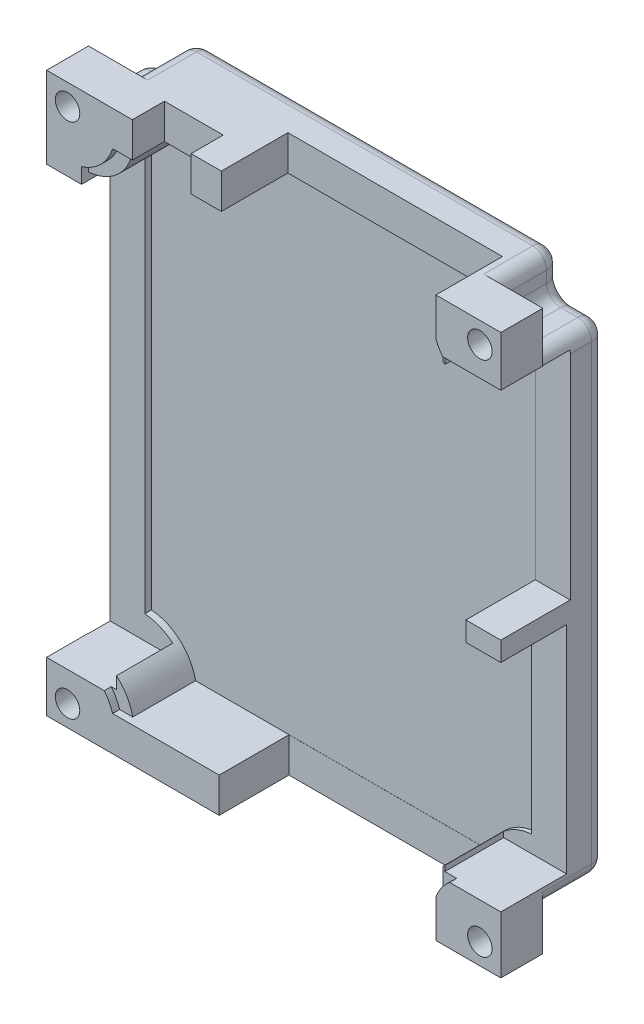
SolidWorks part; units mm, degrees
ref_plane "Front Plane" through (0, 0, 0) normal (0, 0, 1) x (1, 0, 0)
ref_plane "Top Plane" through (0, 0, 0) normal (0, 1, 0) x (1, 0, 0)
ref_plane "Right Plane" through (0, 0, 0) normal (1, 0, 0) x (0, 0, -1)
sketch "Sketch1" plane through (0, 0, 0) normal (0, 0, 1) x (1, 0, 0)
  line L0 (-65, 80) -> (-65, 0)
  line L9 (0, 0) -> (-65, 0)
  line L10 (0, 0) -> (0, 80)
  line L11 (0, 80) -> (-65, 80)
extrude "Boss-Extrude1" add sketch "Sketch1" against normal blind 15
sketch "Sketch2" plane through (0, 0, 0) normal (0, 0, 1) x (1, 0, 0)
  circle A0 centre (-3, 3) radius 1.75
  circle A1 centre (-62, 3) radius 1.75
  circle A2 centre (-62, 77) radius 1.75
  circle A3 centre (-3, 77) radius 1.75
  dimension "D1" = 3.5
  dimension "D2" = 3.5
  dimension "D3" = 3.5
extrude "Cut-Extrude1" cut sketch "Sketch2" against normal up to surface (15 mm away) up to face at (-32.5, 40, -15)
sketch "Sketch3" plane through (0, 0, -15) normal (0, 0, -1) x (-1, 0, 0)
  line L0 (0, 80) -> (65, 80) construction
  line L1 (0, 80) -> (6.4525, 80)
  line L2 (0, 80) -> (0, 74.3584)
  line L3 (0, 74.3584) -> (6.4525, 74.3584)
  line L4 (6.4525, 80) -> (6.4525, 74.3584)
  line L5 (58.5475, 80) -> (65, 80)
  line L6 (58.5475, 80) -> (58.5475, 74.3584)
  line L7 (58.5475, 74.3584) -> (65, 74.3584)
  line L8 (65, 80) -> (65, 74.3584)
  line L9 (65, 80) -> (65, 0) construction
  line L10 (0, 0) -> (0, 80) construction
  line L11 (0, 5.6416) -> (6.4525, 5.6416)
  line L12 (0, 5.6416) -> (0, 0)
  line L13 (0, 0) -> (6.4525, 0)
  line L14 (6.4525, 5.6416) -> (6.4525, 0)
  line L15 (65, 0) -> (0, 0) construction
  line L17 (58.5475, 0) -> (65, 0)
  line L18 (58.5475, 0) -> (58.5475, 5.6416)
  line L19 (58.5475, 5.6416) -> (65, 5.6416)
  line L20 (65, 0) -> (65, 5.6416)
  dimension "D1" = 6.4525
  dimension "D2" = 5.6416
  dimension "D3" = 5.6416
  dimension "D4" = 6.4525
  dimension "D5" = 6.4525
  dimension "D6" = 6.4525
  dimension "D7" = 5.6416
  dimension "D8" = 5.6416
extrude "Cut-Extrude2" cut sketch "Sketch3" against normal blind 9
fillet "Fillet1" radius 2 24 edges at (-3.2263, 74.3584, -15) (-6.4525, 77.1792, -15) (-58.5475, 77.1792, -15) (0, 5.6416, -10.5) (-6.4525, 0, -10.5) (-6.4525, 80, -10.5) (0, 74.3584, -10.5) (-58.5475, 0, -10.5) (-65, 5.6416, -10.5) (-58.5475, 80, -10.5) (-65, 74.3584, -10.5) (-58.5475, 74.3584, -10.5) (-61.7737, 74.3584, -15) (-32.5, 80, -15) (0, 40, -15) (-3.2263, 5.6416, -15) (-6.4525, 2.8208, -15) (-32.5, 0, -15) (-65, 40, -15) (-58.5475, 2.8208, -15) (-61.7737, 5.6416, -15) (-58.5475, 5.6416, -10.5) (-6.4525, 5.6416, -10.5) (-6.4525, 74.3584, -10.5)
shell "Shell1" thickness 5 removed face at (-1.25, 77, 0)
sketch "Sketch4" plane through (0, 0, 0) normal (0, -1, 0) x (1, 0, 0)
  line L0 (-65, 0) -> (0, 0) construction
  line L5 (-9.3, 0) -> (-40.3, 0)
  line L6 (-9.3, 0) -> (-9.3, -9.9889)
  line L7 (-9.3, -9.9889) -> (-40.3, -9.9889)
  line L8 (-40.3, 0) -> (-40.3, -9.9889)
  line L9 (0, -6) -> (0, 0) construction
  dimension "D1" = 9.9889
  dimension "D2" = 31
  dimension "D3" = 9.3
extrude "Cut-Extrude3" cut sketch "Sketch4" against normal blind 9
sketch "Sketch5" plane through (0, 0, 0) normal (1, 0, 0) x (0, 0, -1)
  line L0 (0, 0) -> (0, 80) construction
  line L1 (0, 41.8744) -> (9.9441, 41.8744)
  line L2 (0, 41.8744) -> (0, 72.8388)
  line L3 (0, 72.8388) -> (9.9441, 72.8388)
  line L4 (9.9441, 41.8744) -> (9.9441, 72.8388)
  line L5 (6, 80) -> (0, 80) construction
  line L10 (0, 39.0943) -> (9.4092, 39.0943)
  line L11 (0, 39.0943) -> (0, 8.1871)
  line L12 (0, 8.1871) -> (9.4092, 8.1871)
  line L13 (9.4092, 39.0943) -> (9.4092, 8.1871)
  dimension "D1" = 30.9071
  dimension "D2" = 9.4092
  dimension "D3" = 30.9644
  dimension "D4" = 9.9441
  dimension "D5" = 7.1612
  dimension "D6" = 2.7801
extrude "Cut-Extrude4" cut sketch "Sketch5" against normal blind 9
sketch "Sketch6" plane through (0, 80, 0) normal (0, 1, 0) x (1, 0, 0)
  line L0 (-52.7271, 0) -> (-44.3262, 0)
  line L7 (-39.9937, 9.5259) -> (-9.2937, 9.5259)
  line L8 (-39.9937, 9.5259) -> (-39.9937, 0)
  line L10 (-9.2937, 9.5259) -> (-9.2937, 0)
  line L11 (0, 0) -> (-65, 0) construction
  line L14 (-39.9937, 0) -> (-9.2937, 0)
  line L18 (-65, 6) -> (-65, 0) construction
  line L19 (-52.7271, 4.5913) -> (-44.3262, 4.5913)
  line L20 (-52.7271, 4.5913) -> (-52.7271, 0)
  line L22 (-44.3262, 4.5913) -> (-44.3262, 0)
  dimension "D1" = 8.4009
  dimension "D2" = 4.5913
  dimension "D3" = 12.2729
  dimension "D4" = 4.3324
  dimension "D5" = 30.7
  dimension "D6" = 9.5259
extrude "Cut-Extrude5" cut sketch "Sketch6" against normal blind 9
sketch "Sketch7" plane through (-65, 0, 0) normal (-1, 0, 0) x (0, 0, 1)
  line L0 (-0.4115, 7.239) -> (0, 7.239)
  line L1 (-9.0497, 68.3475) -> (-0.4115, 68.3475)
  line L2 (-9.0497, 68.3475) -> (-9.0497, 7.239)
  line L3 (-9.0497, 7.239) -> (-0.4115, 7.239)
  line L5 (0, 80) -> (0, 0) construction
  line L6 (-0.4115, 68.3475) -> (0, 68.3475)
  line L8 (0, 68.3475) -> (0, 7.239)
  dimension "D1" = 61.1085
  dimension "D2" = 8.6382
  dimension "D3" = 0.4115
  dimension "D4" = 0.4115
  dimension "D5" = 61.1085
extrude "Cut-Extrude6" cut sketch "Sketch7" against normal blind 9
equation "\"D3@Sketch3\"=\"D2@Sketch3\""
equation "\"D4@Sketch3\"=\"D1@Sketch3\""
equation "\"D5@Sketch3\"=\"D1@Sketch3\""
equation "\"D6@Sketch3\"=\"D1@Sketch3\""
equation "\"D7@Sketch3\"=\"D2@Sketch3\""
equation "\"D8@Sketch3\"=\"D3@Sketch3\""
